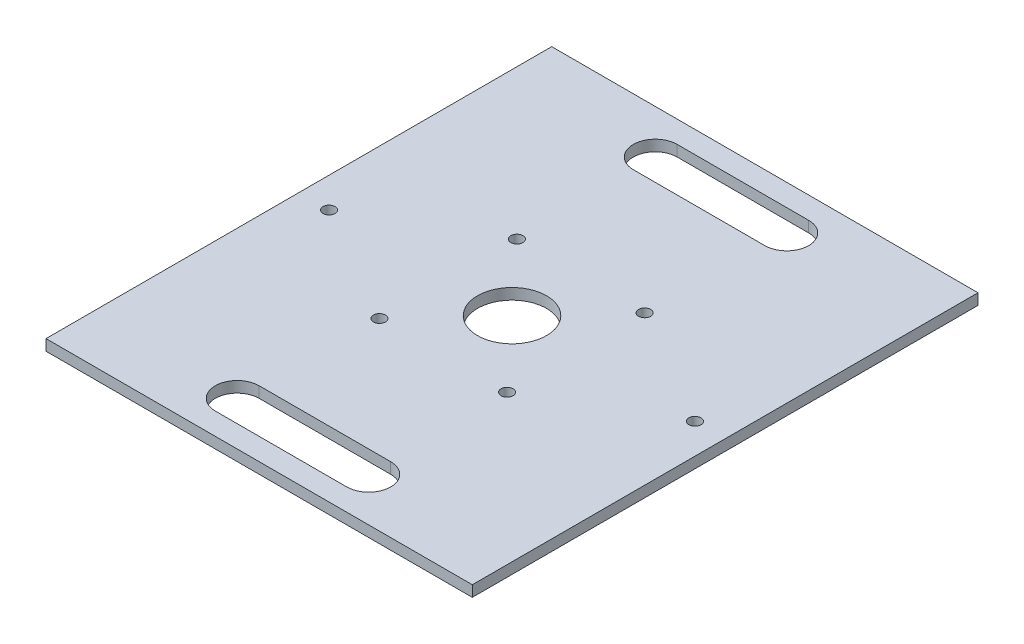
SolidWorks part; units mm, degrees
material "Acrylic (Medium-high impact)"
ref_plane "Front Plane" through (0, 0, 0) normal (0, 0, 1) x (1, 0, 0)
ref_plane "Top Plane" through (0, 0, 0) normal (0, 1, 0) x (1, 0, 0)
ref_plane "Right Plane" through (0, 0, 0) normal (1, 0, 0) x (0, 0, -1)
sketch "Sketch1" plane through (0, 0, 0) normal (0, 1, 0) x (1, 0, 0)
  line L1 (-123.5, -146.5) -> (123.5, -146.5)
  line L2 (-123.5, -146.5) -> (-123.5, 146.5)
  line L3 (-123.5, 146.5) -> (123.5, 146.5)
  line L4 (123.5, -146.5) -> (123.5, 146.5)
  line L5 (-123.5, -146.5) -> (123.5, 146.5) construction
  line L6 (-123.5, 146.5) -> (123.5, -146.5) construction
  point P0 (0, 0)
  dimension "D1" = 293
  dimension "D2" = 247
extrude "Main Base" add sketch "Sketch1" along normal mid plane 6.35
sketch "Sketch2" plane through (0, 3.175, 0) normal (0, 1, 0) x (1, 0, 0)
  line L0 (-38.1, 121.1) -> (38.1, 121.1) construction
  line L1 (-38.1, 133.8) -> (38.1, 133.8)
  line L2 (-38.1, 108.4) -> (38.1, 108.4)
  line L3 (123.5, 146.5) -> (-123.5, 146.5) construction
  line L4 (-1000, 0) -> (49000, 0) construction
  line L5 (-38.1, -121.1) -> (38.1, -121.1) construction
  line L6 (-38.1, -133.8) -> (38.1, -133.8)
  line L7 (-38.1, -108.4) -> (38.1, -108.4)
  arc A0 (-38.1, 133.8) -> (-38.1, 108.4) centre (-38.1, 121.1) ccw
  arc A1 (38.1, 108.4) -> (38.1, 133.8) centre (38.1, 121.1) ccw
  arc A2 (-38.1, -133.8) -> (-38.1, -108.4) centre (-38.1, -121.1) cw
  arc A3 (38.1, -108.4) -> (38.1, -133.8) centre (38.1, -121.1) cw
  point P2 (0, 121.1)
  point P14 (0, -121.1)
  dimension "D2" = 25.4
  dimension "D1" = 25.4
  dimension "D3" = 76.2
extrude "Handles" cut sketch "Sketch2" against normal through all
sketch "Sketch3" plane through (0, 3.175, 0) normal (0, 1, 0) x (1, 0, 0)
  circle A0 centre (0, 0) radius 20
  dimension "D1" = 40
extrude "Camera Hole" cut sketch "Sketch3" against normal through all
sketch "Sketch4" plane through (0, 3.175, 0) normal (0, 1, 0) x (1, 0, 0)
  line L0 (0, -3.4925) -> (0, 3.4925) construction
  circle A0 centre (-60, 0) radius 49 construction
  circle A1 centre (-106, 0) radius 3 construction
  circle A2 centre (-37, 39.8372) radius 3 construction
  circle A3 centre (-37, -39.8372) radius 3 construction
  circle A7 centre (37, -39.8372) radius 3 construction
  circle A8 centre (37, 39.8372) radius 3 construction
  circle A9 centre (106, 0) radius 3 construction
  circle A10 centre (60, 0) radius 49 construction
  point P5 (-23.9213, -50.7179)
  point P6 (0, 0)
  point P7 (-60, 0)
  point P13 (-60, 0)
  point P23 (60, 0)
  point P24 (60, 0)
  dimension "D1" = 98
  dimension "D3" = 6
  dimension "D2" = 60
  dimension "D4" = 3
sketch "Sketch5" plane through (0, 3.175, 0) normal (0, 1, 0) x (1, 0, 0)
  point P0 (-106, 0)
  point P3 (-37, -39.8372)
  point P6 (-37, 39.8372)
  point P10 (37, 39.8372)
  point P13 (37, -39.8372)
  point P16 (106, 0)
hole_wizard "Alignment Holes" positions "Sketch5" profile "Sketch6" hole size "#97" standard "ANSI Inch" end condition through all
sketch "Sketch6" plane through (-106, 3.175, 0) normal (1, 0, 0) x (0, 0, 1)
  line L0 (0, 0) -> (0, 6.35)
  line L1 (0, 6.35) -> (3.5, 6.35)
  line L2 (3.5, 6.35) -> (3.5, 0)
  line L5 (3.5, 0) -> (0, 0)
  line L11 (0, -6.35) -> (0, 107.95) construction
  dimension "Thru Hole Dia." = 7
  dimension "Thru Hole Depth" = 6.35
